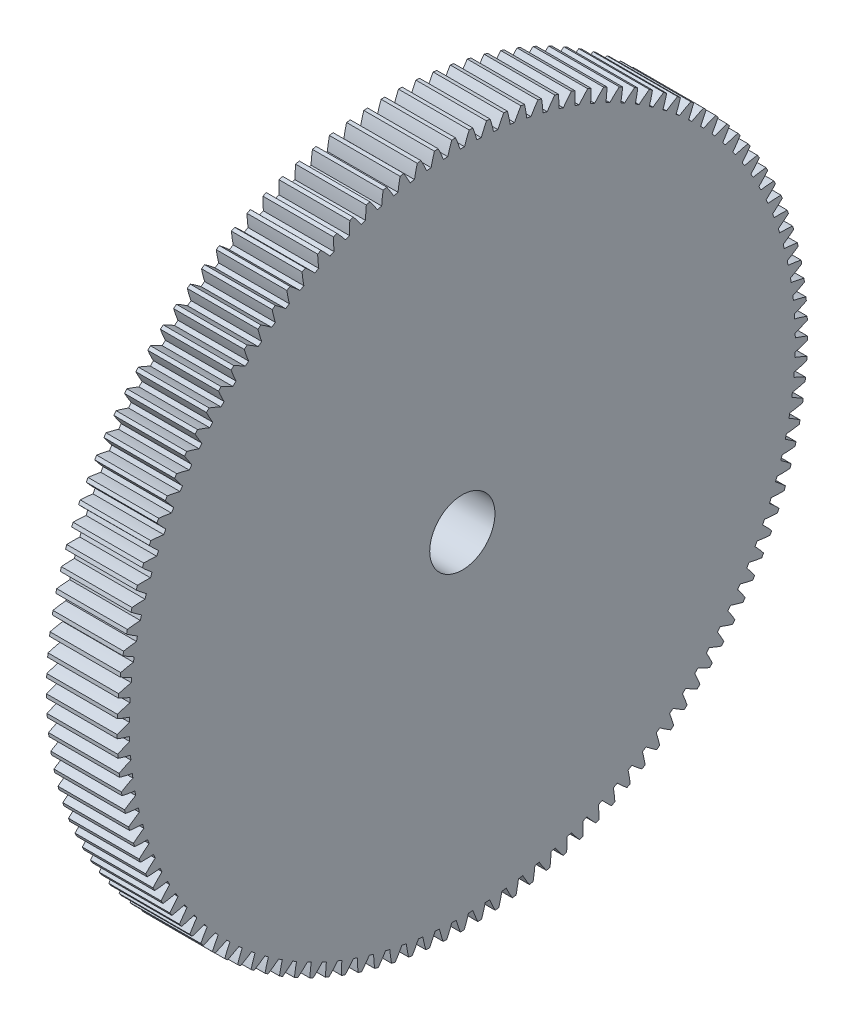
SolidWorks part; units mm, degrees
ref_plane "Plane1" through (0, 0, 0) normal (0, 0, 1) x (1, 0, 0)
ref_plane "Plane2" through (0, 0, 0) normal (0, 1, 0) x (1, 0, 0)
ref_plane "Plane3" through (0, 0, 0) normal (1, 0, 0) x (0, 0, -1)
sketch "HoldingSke" plane through (0, 0, 0) normal (0, 1, 0) x (1, 0, 0)
  line L0 (0, 0) -> (-116.5507, -166.4517)
  line L1 (-15, 0) -> (100, 0) construction
  line L2 (0, 0) -> (-2.1039, 2.3779)
  line L3 (0, 0) -> (-11.863, 4.5341)
  line L4 (0, 0) -> (-4.9534, 7.0742)
  line L5 (0, 0) -> (-47.5972, -17.7524)
  line L6 (0, 0) -> (-34.2154, -23.0853)
  line L7 (-2.1039, 2.3779) -> (8.8308, 51.9872)
  line L8 (-76.2, 54.61) -> (-33.8074, 54.61)
  line L9 (-71.009, 38.7566) -> (-53.1078, 45.2721)
  line L10 (-76.2, 71.12) -> (104.1128, 71.12)
  line L11 (0, 0) -> (-41.275, 0)
  line L12 (-76.2, 101.6) -> (-76.0857, 101.6)
  line L13 (24.9733, 27.94) -> (52.9518, 28.4284)
  line L14 (24.9733, 27.94) -> (24.9746, 27.94)
  line L15 (24.9733, 27.94) -> (100.4006, 29.5858)
  circle A0 centre (0, 0) radius 19.05
  circle A1 centre (0, 0) radius 38.1
  circle A2 centre (0, 0) radius 38.1
  circle A3 centre (0, 0) radius 19.05
  dimension "Num_teeth" = 125
  dimension "H" = 19.05
  dimension "Pitch_radius" = 180.3128
  dimension "Width" = 41.275
  dimension "Thickness" = 41.275
sketch "BasProSke" plane through (0, 0, 0) normal (0, 1, 0) x (1, 0, 0)
  line L0 (-10, 0) -> (60, 0) construction
  line L1 (0, 0) -> (0, 201.6125)
  line L2 (0, 0) -> (41.275, 0)
  line L3 (41.275, 0) -> (41.275, 201.6125)
  line L4 (41.275, 201.6125) -> (0, 201.6125)
  dimension "Thickness" = 41.275
  dimension "Diameter" = 403.225
revolve "Base-Revolve" add sketch "BasProSke" angle 360 about L0
sketch "TooCutSke" plane through (0, 0, 0) normal (1, 0, 0) x (0, 0, -1)
  line L1 (0, 0) -> (0, 107) construction
  line L2 (0, 0) -> (-2.6936, 198.4192) construction
  line L3 (0, 0) -> (-9.9728, 396.7232) construction
  line L4 (-2.6936, 198.4192) -> (-4.9864, 198.3616) construction
  arc A0 (1.2912, 194.4632) -> (-1.2912, 194.4632) centre (0, 0) ccw
  arc A1 (3.9958, 201.5983) -> (-3.9958, 201.5983) centre (0, 0) ccw
  circle A2 centre (0, 0) radius 198.4375 construction
  circle A3 centre (0, 0) radius 186.4703 construction
  arc A4 (-1.2912, 194.4632) -> (-3.9958, 201.5983) centre (-76.7796, 169.9296) ccw
  arc A5 (3.9958, 201.5983) -> (1.2912, 194.4632) centre (76.7796, 169.9296) ccw
extrude "ToothCut" cut sketch "TooCutSke" along normal through all
fillet "Breaks" [suppressed] radius 0.0635 tangent propagation no
fillet "RootFillets" [suppressed] radius 0.795
pattern_circular "TeethCuts" count 125 every 2.88 about axis through (-10, 0, 0) along (1, 0, 0) of "ToothCut", "RootFillets", "Breaks"
sketch "HubNeaOneSke" plane through (0, 0, 0) normal (-1, 0, 0) x (0, 0, 1)
  circle A0 centre (0, 0) radius 38.1
  dimension "Diameter" = 76.2
extrude "HubNearOne" [suppressed] add sketch "HubNeaOneSke" along normal blind 9.5251
sketch "HubNeaBotSke" plane through (0, 0, 0) normal (-1, 0, 0) x (0, 0, 1)
  circle A0 centre (0, 0) radius 38.1
  dimension "Diameter" = 76.2
extrude "HubNearBoth" [suppressed] add sketch "HubNeaBotSke" along normal blind 4.7626
ref_plane "FarPln" through (41.275, 0, 0) normal (1, 0, 0) x (0, 0, -1)
sketch "HubFarSke" plane through (41.275, 0, 0) normal (1, 0, 0) x (0, 0, -1)
  circle A0 centre (0, 0) radius 38.1
  dimension "Diameter" = 76.2
extrude "HubFar" [suppressed] add sketch "HubFarSke" along normal blind 4.7626
sketch "BorSke" plane through (0, 0, 0) normal (1, 0, 0) x (0, 0, -1)
  circle A0 centre (0, 0) radius 19.05
  dimension "Diameter" = 38.1
extrude "Bore" cut sketch "BorSke" along normal mid plane 101.6002
equation "' \"Pitch@HoldingSke\" = 4"
equation "' \"Num_teeth@HoldingSke\" = 12"
equation "' \"Ap@HoldingSke\" =  20"
equation "' \"Ap@HoldingSke\" = 20"
equation "' \"Width@HoldingSke\" = 0.5"
equation "' \"Hub_dia@HoldingSke\"= 1"
equation "' \"Hub_dia@HoldingSke\" = 1"
equation "' \"Overall_len@HoldingSke\" = 1.0"
equation "' \"Bore@HoldingSke\" = 0.75"
equation "' \"T_dim@HoldingSke\" = 0.85"
equation "' \"Width@KeySke\" = 0.25"
equation "' \"Show_teeth@HoldingSke\" = 13"
equation "' \"Backlash@HoldingSke\" = 0.009"
equation "' \"Addendum_fac@HoldingSke\" = 1.0"
equation "' \"Dedendum_fac@HoldingSke\" = 1.25"
equation "' \"Dedendum_add@HoldingSke\" = 0.00005"
equation "' \"Clearance_fac@HoldingSke\" = 0.25"
equation "' \"Pitch@HoldingSke\" = 0.5"
equation "' \"Num_teeth@HoldingSke\" = 23"
equation "' \"Show_teeth@HoldingSke\" = 23"
equation "' \"Backlash@HoldingSke\" = 0.0375"
equation "\"Overcut_dia@TooCutSke\" = (\"Num_teeth@HoldingSke\" + 2 * \"Addendum_fac@HoldingSke\") / \"Pitch@HoldingSke\" + 0.002"
equation "\"Pitch_dia@TooCutSke\" = \"Num_teeth@HoldingSke\" / \"Pitch@HoldingSke\""
equation "\"Base_dia@TooCutSke\" = \"Num_teeth@HoldingSke\" / \"Pitch@HoldingSke\" * cos((\"Ap@HoldingSke\"  * 3.14159265 / 180))"
equation "\"Root_dia@TooCutSke\" = (\"Num_teeth@HoldingSke\" + 2) / \"Pitch@HoldingSke\" - 2 * (\"Addendum_fac@HoldingSke\" + \"Dedendum_fac@HoldingSke\") / \"Pitch@HoldingSke\" - \"Dedendum_add@HoldingSke\" * 2"
equation "\"Half_ang@TooCutSke\" = 180 / \"Num_teeth@HoldingSke\""
equation "\"Half_CT@TooCutSke\" = \"Num_teeth@HoldingSke\" / \"Pitch@HoldingSke\" * sin((3.14159265 / 2 / \"Num_teeth@HoldingSke\")) / 2 - 7 * \"Backlash@HoldingSke\" / 4"
equation "\"Flank_rad@TooCutSke\" = \"Num_teeth@HoldingSke\" / \"Pitch@HoldingSke\" / 5"
equation "\"Radius@RootFillets\" = \"Clearance_fac@HoldingSke\" / \"Pitch@HoldingSke\" + \"Dedendum_add@HoldingSke\""
equation "\"Break_rad@Breaks\" = 0.02 / \"Pitch@HoldingSke\""
equation "\"Thickness@HoldingSke\" = \"Width@HoldingSke\""
equation "\"OAL@HoldingSke\" = \"Thickness@HoldingSke\""
equation "\"MHD@HoldingSke\" = (\"Num_teeth@HoldingSke\" + 2) / \"Pitch@HoldingSke\" - 2 * (\"Addendum_fac@HoldingSke\" + \"Dedendum_fac@HoldingSke\")  / \"Pitch@HoldingSke\" - \"Dedendum_add@HoldingSke\" * 2"
equation "\"MBD@HoldingSke\" = (\"Num_teeth@HoldingSke\" + 2) / \"Pitch@HoldingSke\" - 2 * (\"Addendum_fac@HoldingSke\" + \"Dedendum_fac@HoldingSke\")  / \"Pitch@HoldingSke\" - \"Dedendum_add@HoldingSke\" * 2 - 0.002"
equation "\"MHD@HoldingSke\" = ((sgn( \"MHD@HoldingSke\" - \"Hub_dia@HoldingSke\" )-1)*( \"MHD@HoldingSke\" - \"Hub_dia@HoldingSke\" ))/-2+ \"Hub_dia@HoldingSke\""
equation "\"MBD@HoldingSke\" = ((sgn( \"MBD@HoldingSke\" - \"Bore@HoldingSke\" )-1)*( \"MBD@HoldingSke\" - \"Bore@HoldingSke\" ))/-2+ \"Bore@HoldingSke\""
equation "\"OAL@HoldingSke\" = ((sgn( \"OAL@HoldingSke\" - \"Overall_len@HoldingSke\" )+1)*( \"OAL@HoldingSke\" - \"Overall_len@HoldingSke\" ))/2 + \"Overall_len@HoldingSke\" + 0.000002"
equation "\"Num_teeth@TeethCuts\" = int( \"Show_teeth@HoldingSke\" ) + 1"
equation "\"Num_teeth@TeethCuts\" = ((sgn( \"Num_teeth@TeethCuts\" - \"Num_teeth@HoldingSke\" )-1)*( \"Num_teeth@TeethCuts\" - \"Num_teeth@HoldingSke\" ))/-2+ \"Num_teeth@HoldingSke\""
equation "\"Num_teeth@TeethCuts\" = ((sgn( \"Num_teeth@TeethCuts\" - 2.0)+1)*( \"Num_teeth@TeethCuts\" - 2.0))/2 +2.0"
equation "\"Angle@TeethCuts\" = 360.0 / \"Num_teeth@HoldingSke\""
equation "\"Diameter@BasProSke\" = (\"Num_teeth@HoldingSke\" + 2 * \"Addendum_fac@HoldingSke\") / \"Pitch@HoldingSke\""
equation "\"Thickness@BasProSke\"  = \"Thickness@HoldingSke\""
equation "' \"Fillet_rad@BasProSke\" =  \"Thickness@HoldingSke\" * 0.05"
equation "' \"Fillet_rad@BasProSke\" = \"Thickness@HoldingSke\" * 0.05"
equation "\"MHD@HoldingSke\" = ((sgn( \"MHD@HoldingSke\" - \"Root_dia@TooCutSke\" )-1)*( \"MHD@HoldingSke\" - \"Root_dia@TooCutSke\" ))/-2+ \"Root_dia@TooCutSke\""
equation "\"Diameter@HubNeaOneSke\" = \"MHD@HoldingSke\""
equation "\"Length@HubNearOne\" = \"OAL@HoldingSke\" - \"Thickness@BasProSke\""
equation "\"Diameter@HubNeaBotSke\" = \"MHD@HoldingSke\""
equation "\"Length@HubNearBoth\" = ( \"OAL@HoldingSke\" - \"Thickness@BasProSke\" ) / 2.0"
equation "\"Thickness@FarPln\" = \"Thickness@BasProSke\""
equation "\"Diameter@HubFarSke\" = \"MHD@HoldingSke\""
equation "\"Length@HubFar\" = ( \"OAL@HoldingSke\" - \"Thickness@BasProSke\" ) / 2.0"
equation "\"Diameter@BorSke\" = \"MBD@HoldingSke\""
equation "\"D1@Bore\"= \"OAL@HoldingSke\" * 2.0"
equation "\"D1\"= \"OAL@HoldingSke\" * 2.0"
